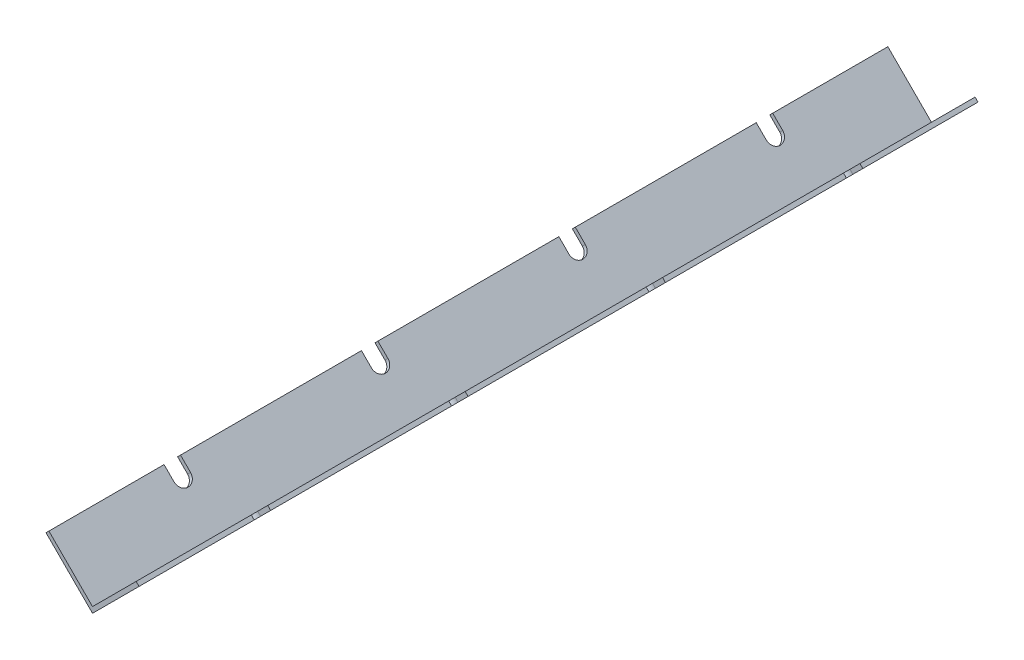
SolidWorks part; units mm, degrees
material "6061 Alloy"
ref_plane "Front Plane" through (0, 0, 0) normal (0, 0, 1) x (1, 0, 0)
ref_plane "Top Plane" through (0, 0, 0) normal (0, 1, 0) x (1, 0, 0)
ref_plane "Right Plane" through (0, 0, 0) normal (1, 0, 0) x (0, 0, -1)
sketch "Sketch1" plane through (0, 0, 0) normal (0, 0, 1) x (1, 0, 0)
  line L0 (0, 0) -> (-17.9605, 17.9605)
  line L1 (-17.9605, 17.9605) -> (-16.838, 19.083)
  line L2 (-16.838, 19.083) -> (0, 2.2451)
  line L3 (0, 2.2451) -> (16.838, 19.083)
  line L4 (16.838, 19.083) -> (17.9605, 17.9605)
  line L5 (17.9605, 17.9605) -> (0, 0)
  dimension "D1" = 1.5875
  dimension "D2" = 25.4
extrude "Boss-Extrude1" add sketch "Sketch1" along normal blind 323.85
sketch "Sketch3" plane through (0, 0, 0) normal (1, 0, 0) x (0, 0, -1)
  line L0 (-276.225, 16.162) -> (-323.85, 16.162) construction
  line L6 (-196.85, 19.083) -> (-203.2, 19.083)
  line L7 (-203.2, 19.083) -> (-203.2, 16.162)
  line L8 (-196.85, 16.162) -> (-196.85, 19.083)
  line L9 (-120.65, 19.083) -> (-127, 19.083)
  line L10 (-127, 19.083) -> (-127, 16.162)
  line L11 (-120.65, 16.162) -> (-120.65, 19.083)
  line L16 (-44.45, 19.083) -> (-50.8, 19.083)
  line L17 (-50.8, 19.083) -> (-50.8, 16.162)
  line L22 (-44.45, 16.162) -> (-44.45, 19.083)
  line L28 (-323.85, 0) -> (-323.85, 17.9605) construction
  line L29 (-276.225, 16.162) -> (-200.025, 16.162) construction
  line L30 (-279.4, 19.083) -> (-279.4, 16.162)
  line L31 (-323.85, 19.083) -> (0, 19.083) construction
  line L32 (-273.05, 16.162) -> (-273.05, 19.083)
  line L33 (-273.05, 19.083) -> (-279.4, 19.083)
  line L34 (-200.025, 16.162) -> (-123.825, 16.162) construction
  line L35 (-123.825, 16.162) -> (-47.625, 16.162) construction
  line L36 (-47.625, 16.162) -> (0, 16.162) construction
  line L37 (0, 0) -> (0, 17.9605) construction
  arc A0 (-279.4, 16.162) -> (-273.05, 16.162) centre (-276.225, 16.162) ccw
  arc A1 (-203.2, 16.162) -> (-196.85, 16.162) centre (-200.025, 16.162) ccw
  arc A2 (-127, 16.162) -> (-120.65, 16.162) centre (-123.825, 16.162) ccw
  arc A3 (-50.8, 16.162) -> (-44.45, 16.162) centre (-47.625, 16.162) ccw
  dimension "D1" = 76.2
  dimension "D2" = 6.096
  dimension "D4" = 6.35
extrude "Cut-Extrude2" cut sketch "Sketch3" against normal through all both and the other way through all
sketch "Sketch4" plane through (0, 0, 0) normal (0.7071, -0.7071, 0) x (0, 0, -1)
  line L0 (-279.4, 25.4) -> (-279.4, 19.954)
  line L1 (-273.05, 19.954) -> (-273.05, 25.4)
  line L17 (-273.05, 25.4) -> (-279.4, 25.4)
  line L21 (-203.2, 25.4) -> (-203.2, 19.954)
  line L22 (-196.85, 19.954) -> (-196.85, 25.4)
  line L23 (-196.85, 25.4) -> (-203.2, 25.4)
  line L24 (-127, 25.4) -> (-127, 19.954)
  line L25 (-120.65, 19.954) -> (-120.65, 25.4)
  line L26 (-120.65, 25.4) -> (-127, 25.4)
  line L27 (-50.8, 25.4) -> (-50.8, 19.954)
  line L28 (-44.45, 19.954) -> (-44.45, 25.4)
  line L29 (-44.45, 25.4) -> (-50.8, 25.4)
  line L30 (-50.8, 22.8566) -> (-50.8, 25.4) construction
  arc A0 (-279.4, 19.954) -> (-273.05, 19.954) centre (-276.225, 19.954) ccw
  arc A2 (-203.2, 19.954) -> (-196.85, 19.954) centre (-200.025, 19.954) ccw
  arc A5 (-127, 19.954) -> (-120.65, 19.954) centre (-123.825, 19.954) ccw
  arc A6 (-50.8, 19.954) -> (-44.45, 19.954) centre (-47.625, 19.954) ccw
  ellipse E3 centre (-276.225, 21.2691) end of major axis (-276.225, 25.7592) minor radius 3.175 (-279.4, 21.2691) -> (-273.05, 21.2691) ccw construction
  dimension "D1" = 4
extrude "Cut-Extrude3" cut sketch "Sketch4" against normal through all both and the other way through all
mirror "Mirror1" about plane through (0, 0, 0) normal (1, 0, 0) of "Cut-Extrude3"
